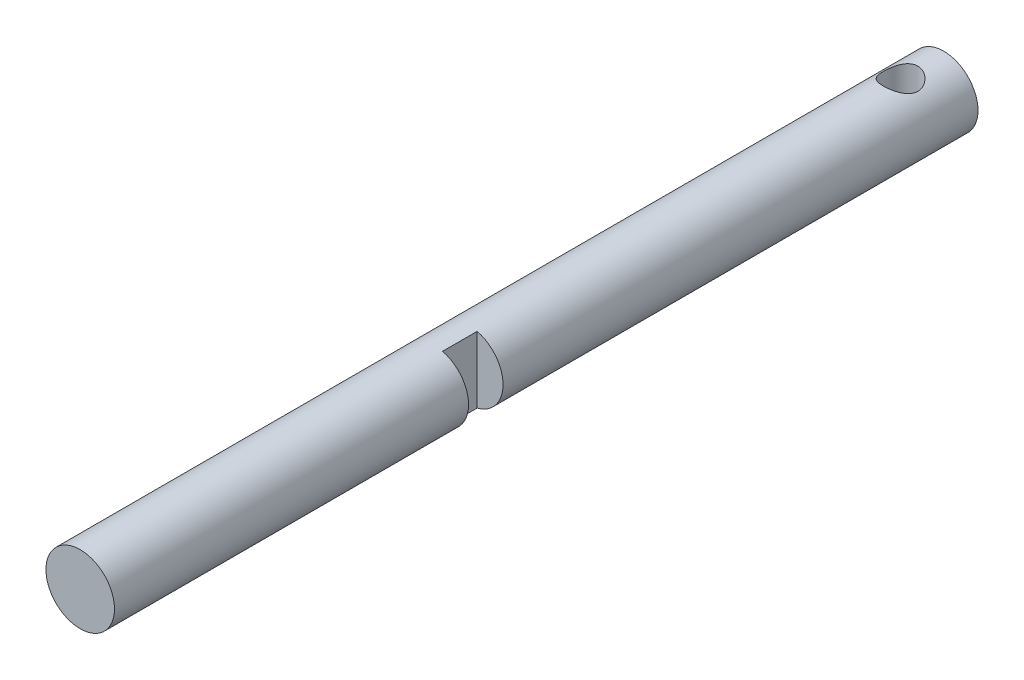
SolidWorks part; units mm, degrees
ref_plane "Front Plane" through (0, 0, 0) normal (0, 0, 1) x (1, 0, 0)
ref_plane "Top Plane" through (0, 0, 0) normal (0, 1, 0) x (1, 0, 0)
ref_plane "Right Plane" through (0, 0, 0) normal (1, 0, 0) x (0, 0, -1)
sketch "Sketch1" plane through (0, 0, 0) normal (0, 0, 1) x (1, 0, 0)
  circle A0 centre (0, 0) radius 3.9688
  dimension "D1" = 7.9375
extrude "Boss-Extrude1" add sketch "Sketch1" along normal blind 100
sketch "Sketch2" plane through (0, 0, 0) normal (0, 1, 0) x (1, 0, 0)
  line L0 (0, 0) -> (0, -10.1) construction
  line L1 (-5.08, -10.1) -> (5.08, -10.1)
  line L2 (-5.08, -10.1) -> (-5.08, 0)
  line L3 (-5.08, 0) -> (5.08, 0)
  line L4 (5.08, -10.1) -> (5.08, 0)
  dimension "D1" = 10.16
  dimension "D2" = 10.1
extrude "Cut-Extrude1" [suppressed] cut sketch "Sketch2" against normal blind 2 and the other way blind 2
sketch "Sketch3" plane through (0, 0, 0) normal (0, 1, 0) x (1, 0, 0)
  circle A0 centre (0, -5) radius 2
  dimension "D1" = 4
  dimension "D2" = 5
extrude "Cut-Extrude2" cut sketch "Sketch3" against normal through all and the other way through all
sketch "Sketch5" plane through (0, 0, 0) normal (0, 1, 0) x (1, 0, 0)
  line L0 (3.9688, -59) -> (0.9688, -59)
  line L2 (3.9688, -55) -> (3.9688, -59)
  line L3 (3.9688, -100) -> (3.9688, 0) construction
  line L4 (0.9688, -59) -> (0.9688, -55)
  line L5 (0.9688, -55) -> (3.9688, -55)
  dimension "D1" = 3
  dimension "D2" = 4
  dimension "D3" = 55
extrude "Cut-Extrude3" cut sketch "Sketch5" against normal through all and the other way through all
